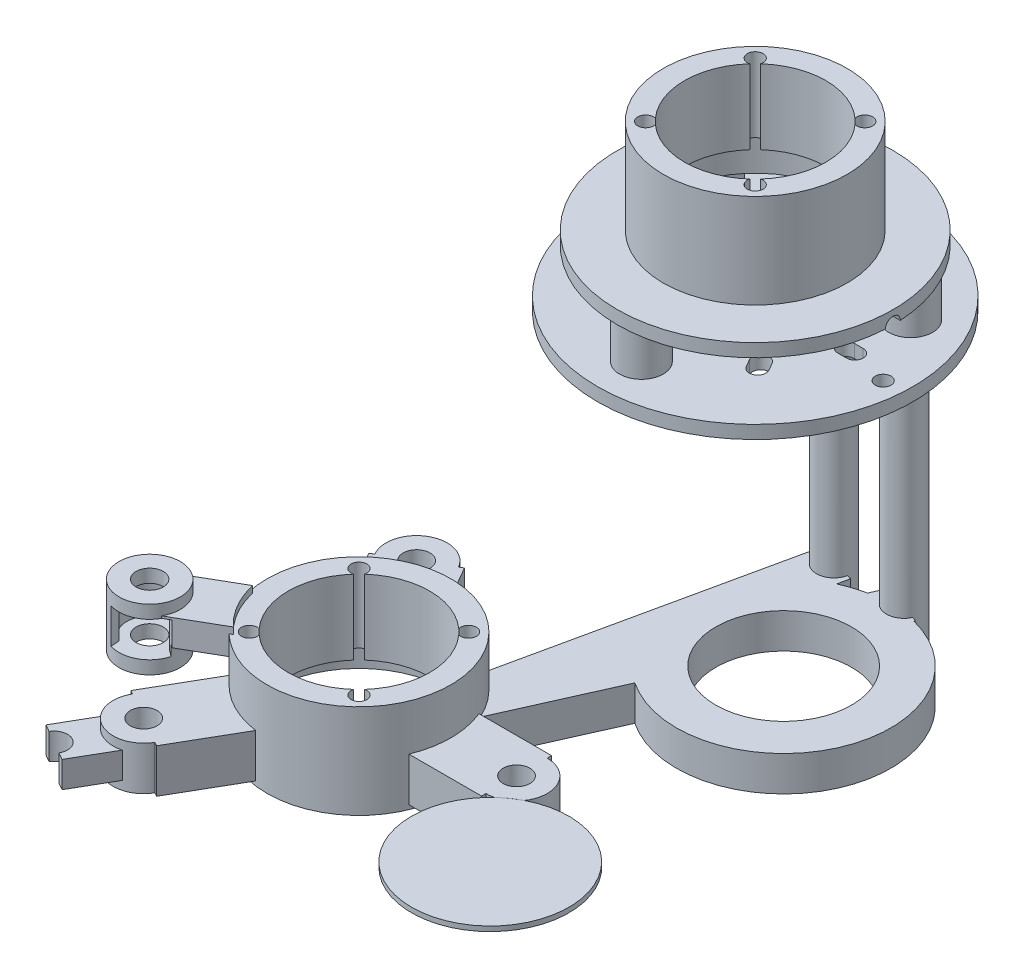
SolidWorks part; units mm, degrees
other "Driven Wheel Carrier and Motor Mount"
ref_plane "Front Plane" through (0, 0, 0) normal (0, 0, 1) x (1, 0, 0)
ref_plane "Top Plane" through (0, 0, 0) normal (0, 1, 0) x (1, 0, 0)
ref_plane "Right Plane" through (0, 0, 0) normal (1, 0, 0) x (0, 0, -1)
sketch3d "Carrier Inboard Frame Sketch datum points"
  point P0 (-56.2917, 132, 0)
  point P1 (-46.2917, 132, 0)
  point P2 (-56.2917, 132, -10)
ref_plane "Carrier Inboard Frame Sketch plane" through (0, 132, 0) normal (0, 1, 0) x (1, 0, 0)
sketch "Carrier Inboard Frame Sketch" plane through (0, 132, 0) normal (0, 1, 0) x (1, 0, 0)
  line L0 (-30.9178, 80.0952) -> (-31.8949, 80.3078)
  line L1 (-22.1235, 78.1819) -> (-23.1006, 78.3945)
  line L2 (-14.6632, 80.8722) -> (-15.5767, 81.279)
  line L3 (-6.4416, 77.2108) -> (-7.3551, 77.6176)
  line L4 (-31.8949, 80.3078) -> (-45.4534, 17.987)
  line L5 (-22.7017, 75.5241) -> (-22.1235, 78.1819)
  line L6 (-6.5333, 77.0049) -> (-6.4416, 77.2108)
  line L7 (-15.5767, 81.279) -> (-17.3672, 77.2584)
  line L8 (-67.3634, -35.1769) -> (-59.0717, -20.8152)
  line L9 (-72.9281, -12.8152) -> (-81.2199, -27.1769)
  line L10 (-81.2199, 27.1769) -> (-72.9281, 12.8152)
  line L11 (-59.0717, 20.8152) -> (-67.3634, 35.1769)
  line L12 (-37.065, 8.446) -> (-26.1713, 32.9078)
  line L13 (-20.2917, 8) -> (-36.8752, 8)
  line L14 (-36.8752, -8) -> (-20.2917, -8)
  line L15 (-20.2917, 7) -> (-20.2917, 8)
  line L16 (-20.2917, -8) -> (-20.2917, -7)
  line L17 (-80.3538, 27.6769) -> (-81.2199, 27.1769)
  line L18 (-67.3634, 35.1769) -> (-68.2295, 34.6769)
  line L19 (-68.2295, -34.6769) -> (-67.3634, -35.1769)
  line L20 (-81.2199, -27.1769) -> (-80.3538, -27.6769)
  line L21 (-14.5666, -4.0278) -> (-14.5523, -4.0074)
  line L22 (-81.0713, -32.9196) -> (-86.1218, -41.6673)
  line L23 (-77.4615, -46.6673) -> (-72.411, -37.9196)
  line L24 (-86.1218, -41.6673) -> (-84.4763, -42.6173)
  line L25 (-79.107, -45.7173) -> (-77.4615, -46.6673)
  arc A0 (-26.8341, 83.2411) -> (-30.9178, 80.0952) centre (-27.0092, 79.2449) ccw
  arc A1 (-23.1006, 78.3945) -> (-26.8341, 83.2411) centre (-27.0092, 79.2449) ccw
  arc A2 (-8.6179, 82.4514) -> (-14.6632, 80.8722) centre (-11.0092, 79.2449) ccw
  arc A3 (-7.3551, 77.6176) -> (-8.6179, 82.4514) centre (-11.0092, 79.2449) ccw
  arc A4 (-59.0717, 20.8152) -> (-45.4534, 17.987) centre (-56.2917, 0) cw
  arc A5 (-56.2917, -21) -> (-59.0717, -20.8152) centre (-56.2917, 0) cw
  arc A6 (-36.8752, -8) -> (-56.2917, -21) centre (-56.2917, 0) cw
  arc A7 (-72.9281, -12.8152) -> (-72.9281, 12.8152) centre (-56.2917, 0) cw
  arc A8 (-37.065, 8.446) -> (-36.8752, 8) centre (-56.2917, 0) cw
  arc A9 (-6.5333, 77.0049) -> (-26.1713, 32.9078) centre (-12.5092, 53.2449) cw
  arc A10 (-22.7017, 75.5241) -> (-17.3672, 77.2584) centre (-12.5092, 53.2449) cw
  circle A11 centre (-12.5092, 53.2449) radius 15.5
  arc A12 (-67.0768, -12.0209) -> (-68.3126, -10.7851) centre (-68.8074, -12.5158) cw
  arc A13 (-45.5065, -12.0209) -> (-67.0768, -12.0209) centre (-56.2917, 0) cw
  arc A14 (-68.3126, -10.7851) -> (-68.3126, 10.7851) centre (-56.2917, 0) cw
  arc A15 (-68.3126, 10.7851) -> (-67.0768, 12.0209) centre (-68.8074, 12.5158) cw
  arc A16 (-67.0768, 12.0209) -> (-45.5065, 12.0209) centre (-56.2917, 0) cw
  arc A17 (-45.5065, 12.0209) -> (-44.2707, 10.7851) centre (-43.7759, 12.5158) cw
  arc A18 (-44.2707, 10.7851) -> (-44.2707, -10.7851) centre (-56.2917, 0) cw
  arc A19 (-44.2707, -10.7851) -> (-45.5065, -12.0209) centre (-43.7759, -12.5158) cw
  arc A20 (-20.2917, -7) -> (-14.5666, -4.0278) centre (-20.2917, 0) ccw
  arc A21 (-14.5523, -4.0074) -> (-20.2917, 7) centre (-20.2917, 0) ccw
  circle A22 centre (-20.2917, 0) radius 3.05
  arc A23 (-68.2295, 34.6769) -> (-80.3538, 27.6769) centre (-74.2917, 31.1769) ccw
  circle A24 centre (-74.2917, 31.1769) radius 3.05
  arc A25 (-80.3538, -27.6769) -> (-81.0713, -32.9196) centre (-74.2917, -31.1769) ccw
  arc A26 (-72.411, -37.9196) -> (-68.2295, -34.6769) centre (-74.2917, -31.1769) ccw
  circle A27 centre (-74.2917, -31.1769) radius 3.05
  arc A28 (-84.4763, -42.6173) -> (-79.107, -45.7173) centre (-81.7917, -44.1673) cw
extrude "Carrier Inboard Frame" add sketch "Carrier Inboard Frame Sketch" against normal blind 4.5 separate body
sketch3d "Carrier Guide and Pivot Frame 2 Sketch datum points"
  point P0 (-56.2917, 132, 0)
  point P1 (-46.2917, 132, 0)
  point P2 (-56.2917, 132, -10)
ref_plane "Carrier Guide and Pivot Frame 2 Sketch plane" through (0, 132, 0) normal (0, 1, 0) x (1, 0, 0)
sketch "Carrier Guide and Pivot Frame 2 Sketch" plane through (0, 132, 0) normal (0, 1, 0) x (1, 0, 0)
  line L0 (-30.9178, 80.0952) -> (-31.8949, 80.3078)
  line L1 (-22.1235, 78.1819) -> (-23.1006, 78.3945)
  line L2 (-14.6632, 80.8722) -> (-15.5767, 81.279)
  line L3 (-6.4416, 77.2108) -> (-7.3551, 77.6176)
  line L4 (-31.8949, 80.3078) -> (-45.4534, 17.987)
  line L5 (-22.7017, 75.5241) -> (-22.1235, 78.1819)
  line L6 (-6.5333, 77.0049) -> (-6.4416, 77.2108)
  line L7 (-15.5767, 81.279) -> (-17.3672, 77.2584)
  line L8 (-67.3634, -35.1769) -> (-59.0717, -20.8152)
  line L9 (-72.9281, -12.8152) -> (-81.2199, -27.1769)
  line L10 (-81.2199, 27.1769) -> (-72.9281, 12.8152)
  line L11 (-59.0717, 20.8152) -> (-67.3634, 35.1769)
  line L12 (-37.065, 8.446) -> (-26.1713, 32.9078)
  line L13 (-20.2917, 8) -> (-36.8752, 8)
  line L14 (-36.8752, -8) -> (-20.2917, -8)
  line L15 (-20.2917, 7) -> (-20.2917, 8)
  line L16 (-20.2917, -8) -> (-20.2917, -7)
  line L17 (-80.3538, 27.6769) -> (-81.2199, 27.1769)
  line L18 (-67.3634, 35.1769) -> (-68.2295, 34.6769)
  line L19 (-68.2295, -34.6769) -> (-67.3634, -35.1769)
  line L20 (-81.2199, -27.1769) -> (-80.3538, -27.6769)
  line L21 (-14.5666, -4.0278) -> (-14.5523, -4.0074)
  arc A0 (-26.8341, 83.2411) -> (-30.9178, 80.0952) centre (-27.0092, 79.2449) ccw
  arc A1 (-23.1006, 78.3945) -> (-26.8341, 83.2411) centre (-27.0092, 79.2449) ccw
  arc A2 (-8.6179, 82.4514) -> (-14.6632, 80.8722) centre (-11.0092, 79.2449) ccw
  arc A3 (-7.3551, 77.6176) -> (-8.6179, 82.4514) centre (-11.0092, 79.2449) ccw
  arc A4 (-59.0717, 20.8152) -> (-45.4534, 17.987) centre (-56.2917, 0) cw
  arc A5 (-56.2917, -21) -> (-59.0717, -20.8152) centre (-56.2917, 0) cw
  arc A6 (-36.8752, -8) -> (-56.2917, -21) centre (-56.2917, 0) cw
  arc A7 (-72.9281, -12.8152) -> (-72.9281, 12.8152) centre (-56.2917, 0) cw
  arc A8 (-37.065, 8.446) -> (-36.8752, 8) centre (-56.2917, 0) cw
  arc A9 (-6.5333, 77.0049) -> (-26.1713, 32.9078) centre (-12.5092, 53.2449) cw
  arc A10 (-22.7017, 75.5241) -> (-17.3672, 77.2584) centre (-12.5092, 53.2449) cw
  circle A11 centre (-12.5092, 53.2449) radius 15.5
  arc A12 (-67.0768, -12.0209) -> (-68.3126, -10.7851) centre (-68.8074, -12.5158) cw
  arc A13 (-45.5065, -12.0209) -> (-67.0768, -12.0209) centre (-56.2917, 0) cw
  arc A14 (-68.3126, -10.7851) -> (-68.3126, 10.7851) centre (-56.2917, 0) cw
  arc A15 (-68.3126, 10.7851) -> (-67.0768, 12.0209) centre (-68.8074, 12.5158) cw
  arc A16 (-67.0768, 12.0209) -> (-45.5065, 12.0209) centre (-56.2917, 0) cw
  arc A17 (-45.5065, 12.0209) -> (-44.2707, 10.7851) centre (-43.7759, 12.5158) cw
  arc A18 (-44.2707, 10.7851) -> (-44.2707, -10.7851) centre (-56.2917, 0) cw
  arc A19 (-44.2707, -10.7851) -> (-45.5065, -12.0209) centre (-43.7759, -12.5158) cw
  arc A20 (-20.2917, -7) -> (-14.5666, -4.0278) centre (-20.2917, 0) ccw
  arc A21 (-14.5523, -4.0074) -> (-20.2917, 7) centre (-20.2917, 0) ccw
  circle A22 centre (-20.2917, 0) radius 3.05
  arc A23 (-68.2295, 34.6769) -> (-80.3538, 27.6769) centre (-74.2917, 31.1769) ccw
  circle A24 centre (-74.2917, 31.1769) radius 3.05
  arc A25 (-80.3538, -27.6769) -> (-72.411, -37.9196) centre (-74.2917, -31.1769) ccw
  arc A26 (-72.411, -37.9196) -> (-68.2295, -34.6769) centre (-74.2917, -31.1769) ccw
  circle A27 centre (-74.2917, -31.1769) radius 3.05
extrude "Carrier Guide and Pivot Frame 2" add sketch "Carrier Guide and Pivot Frame 2 Sketch" along normal blind 0.9
sketch3d "Carrier Guide and Pivot Frame 3 Sketch datum points"
  point P0 (-56.2917, 132.9, 0)
  point P1 (-46.2917, 132.9, 0)
  point P2 (-56.2917, 132.9, -10)
ref_plane "Carrier Guide and Pivot Frame 3 Sketch plane" through (0, 132.9, 0) normal (0, 1, 0) x (1, 0, 0)
sketch "Carrier Guide and Pivot Frame 3 Sketch" plane through (0, 132.9, 0) normal (0, 1, 0) x (1, 0, 0)
  line L0 (-30.9178, 80.0952) -> (-31.8949, 80.3078)
  line L1 (-22.1235, 78.1819) -> (-23.1006, 78.3945)
  line L2 (-14.6632, 80.8722) -> (-15.5767, 81.279)
  line L3 (-6.4416, 77.2108) -> (-7.3551, 77.6176)
  line L4 (-31.8949, 80.3078) -> (-45.4534, 17.987)
  line L5 (-22.7017, 75.5241) -> (-22.1235, 78.1819)
  line L6 (-6.5333, 77.0049) -> (-6.4416, 77.2108)
  line L7 (-15.5767, 81.279) -> (-17.3672, 77.2584)
  line L8 (-67.3634, -35.1769) -> (-59.0717, -20.8152)
  line L9 (-72.9281, -12.8152) -> (-81.2199, -27.1769)
  line L10 (-81.2199, 27.1769) -> (-72.9281, 12.8152)
  line L11 (-59.0717, 20.8152) -> (-67.3634, 35.1769)
  line L12 (-37.065, 8.446) -> (-26.1713, 32.9078)
  line L13 (-20.2917, 8) -> (-36.8752, 8)
  line L14 (-36.8752, -8) -> (-20.2917, -8)
  line L15 (-20.2917, 7) -> (-20.2917, 8)
  line L16 (-20.2917, -8) -> (-20.2917, -7)
  line L17 (-80.3538, 27.6769) -> (-81.2199, 27.1769)
  line L18 (-67.3634, 35.1769) -> (-68.2295, 34.6769)
  line L19 (-68.2295, -34.6769) -> (-67.3634, -35.1769)
  line L20 (-81.2199, -27.1769) -> (-80.3538, -27.6769)
  arc A0 (-26.8341, 83.2411) -> (-30.9178, 80.0952) centre (-27.0092, 79.2449) ccw
  arc A1 (-23.1006, 78.3945) -> (-26.8341, 83.2411) centre (-27.0092, 79.2449) ccw
  arc A2 (-8.6179, 82.4514) -> (-14.6632, 80.8722) centre (-11.0092, 79.2449) ccw
  arc A3 (-7.3551, 77.6176) -> (-8.6179, 82.4514) centre (-11.0092, 79.2449) ccw
  arc A4 (-59.0717, 20.8152) -> (-45.4534, 17.987) centre (-56.2917, 0) cw
  arc A5 (-56.2917, -21) -> (-59.0717, -20.8152) centre (-56.2917, 0) cw
  arc A6 (-36.8752, -8) -> (-56.2917, -21) centre (-56.2917, 0) cw
  arc A7 (-72.9281, -12.8152) -> (-72.9281, 12.8152) centre (-56.2917, 0) cw
  arc A8 (-37.065, 8.446) -> (-36.8752, 8) centre (-56.2917, 0) cw
  arc A9 (-6.5333, 77.0049) -> (-26.1713, 32.9078) centre (-12.5092, 53.2449) cw
  arc A10 (-22.7017, 75.5241) -> (-17.3672, 77.2584) centre (-12.5092, 53.2449) cw
  circle A11 centre (-12.5092, 53.2449) radius 15.5
  arc A12 (-67.0768, -12.0209) -> (-68.3126, -10.7851) centre (-68.8074, -12.5158) cw
  arc A13 (-45.5065, -12.0209) -> (-67.0768, -12.0209) centre (-56.2917, 0) cw
  arc A14 (-68.3126, -10.7851) -> (-68.3126, 10.7851) centre (-56.2917, 0) cw
  arc A15 (-68.3126, 10.7851) -> (-67.0768, 12.0209) centre (-68.8074, 12.5158) cw
  arc A16 (-67.0768, 12.0209) -> (-45.5065, 12.0209) centre (-56.2917, 0) cw
  arc A17 (-45.5065, 12.0209) -> (-44.2707, 10.7851) centre (-43.7759, 12.5158) cw
  arc A18 (-44.2707, 10.7851) -> (-44.2707, -10.7851) centre (-56.2917, 0) cw
  arc A19 (-44.2707, -10.7851) -> (-45.5065, -12.0209) centre (-43.7759, -12.5158) cw
  arc A20 (-20.2917, -7) -> (-18.4908, -6.7644) centre (-20.2917, 0) ccw
  arc A21 (-14.5523, -4.0074) -> (-20.2917, 7) centre (-20.2917, 0) ccw
  arc A22 (-18.4908, -6.7644) -> (-14.5523, -4.0074) centre (-6.2917, -20) ccw
  circle A23 centre (-20.2917, 0) radius 3.05
  arc A24 (-68.2295, 34.6769) -> (-80.3538, 27.6769) centre (-74.2917, 31.1769) ccw
  circle A25 centre (-74.2917, 31.1769) radius 3.05
  arc A26 (-80.3538, -27.6769) -> (-72.411, -37.9196) centre (-74.2917, -31.1769) ccw
  arc A27 (-72.411, -37.9196) -> (-68.2295, -34.6769) centre (-74.2917, -31.1769) ccw
  circle A28 centre (-74.2917, -31.1769) radius 3.05
extrude "Carrier Guide and Pivot Frame 3" add sketch "Carrier Guide and Pivot Frame 3 Sketch" along normal blind 0.1
sketch3d "Carrier Guide and Pivot Frame 4 Sketch datum points"
  point P0 (-56.2917, 133, 0)
  point P1 (-46.2917, 133, 0)
  point P2 (-56.2917, 133, -10)
ref_plane "Carrier Guide and Pivot Frame 4 Sketch plane" through (0, 133, 0) normal (0, 1, 0) x (1, 0, 0)
sketch "Carrier Guide and Pivot Frame 4 Sketch" plane through (0, 133, 0) normal (0, 1, 0) x (1, 0, 0)
  line L0 (-67.3634, -35.1769) -> (-59.0717, -20.8152)
  line L1 (-72.9281, -12.8152) -> (-81.2199, -27.1769)
  line L2 (-81.2199, 27.1769) -> (-72.9281, 12.8152)
  line L3 (-59.0717, 20.8152) -> (-67.3634, 35.1769)
  line L4 (-20.2917, 8) -> (-36.8752, 8)
  line L5 (-36.8752, -8) -> (-20.2917, -8)
  line L6 (-20.2917, 7) -> (-20.2917, 8)
  line L7 (-20.2917, -8) -> (-20.2917, -7)
  line L8 (-80.3538, 27.6769) -> (-81.2199, 27.1769)
  line L9 (-67.3634, 35.1769) -> (-68.2295, 34.6769)
  line L10 (-68.2295, -34.6769) -> (-67.3634, -35.1769)
  line L11 (-81.2199, -27.1769) -> (-80.3538, -27.6769)
  circle A0 centre (-27.0092, 79.2449) radius 4
  circle A1 centre (-11.0092, 79.2449) radius 4
  arc A2 (-56.2917, -21) -> (-59.0717, -20.8152) centre (-56.2917, 0) cw
  arc A3 (-36.8752, -8) -> (-56.2917, -21) centre (-56.2917, 0) cw
  arc A4 (-72.9281, -12.8152) -> (-72.9281, 12.8152) centre (-56.2917, 0) cw
  arc A5 (-59.0717, 20.8152) -> (-36.8752, 8) centre (-56.2917, 0) cw
  arc A6 (-67.0768, -12.0209) -> (-68.3126, -10.7851) centre (-68.8074, -12.5158) cw
  arc A7 (-45.5065, -12.0209) -> (-67.0768, -12.0209) centre (-56.2917, 0) cw
  arc A8 (-68.3126, -10.7851) -> (-68.3126, 10.7851) centre (-56.2917, 0) cw
  arc A9 (-68.3126, 10.7851) -> (-67.0768, 12.0209) centre (-68.8074, 12.5158) cw
  arc A10 (-67.0768, 12.0209) -> (-45.5065, 12.0209) centre (-56.2917, 0) cw
  arc A11 (-45.5065, 12.0209) -> (-44.2707, 10.7851) centre (-43.7759, 12.5158) cw
  arc A12 (-44.2707, 10.7851) -> (-44.2707, -10.7851) centre (-56.2917, 0) cw
  arc A13 (-44.2707, -10.7851) -> (-45.5065, -12.0209) centre (-43.7759, -12.5158) cw
  arc A14 (-20.2917, -7) -> (-18.4908, -6.7644) centre (-20.2917, 0) ccw
  arc A15 (-14.5523, -4.0074) -> (-20.2917, 7) centre (-20.2917, 0) ccw
  arc A16 (-18.4908, -6.7644) -> (-14.5523, -4.0074) centre (-6.2917, -20) ccw
  circle A17 centre (-20.2917, 0) radius 3.05
  arc A18 (-68.2295, 34.6769) -> (-80.3538, 27.6769) centre (-74.2917, 31.1769) ccw
  circle A19 centre (-74.2917, 31.1769) radius 3.05
  arc A20 (-80.3538, -27.6769) -> (-72.411, -37.9196) centre (-74.2917, -31.1769) ccw
  arc A21 (-72.411, -37.9196) -> (-68.2295, -34.6769) centre (-74.2917, -31.1769) ccw
  circle A22 centre (-74.2917, -31.1769) radius 3.05
extrude "Carrier Guide and Pivot Frame 4" add sketch "Carrier Guide and Pivot Frame 4 Sketch" along normal blind 1
sketch3d "Carrier Guide and Pivot Frame 5 Sketch datum points"
  point P0 (-56.2917, 134, 0)
  point P1 (-46.2917, 134, 0)
  point P2 (-56.2917, 134, -10)
ref_plane "Carrier Guide and Pivot Frame 5 Sketch plane" through (0, 134, 0) normal (0, 1, 0) x (1, 0, 0)
sketch "Carrier Guide and Pivot Frame 5 Sketch" plane through (0, 134, 0) normal (0, 1, 0) x (1, 0, 0)
  circle A0 centre (-27.0092, 79.2449) radius 4
  circle A1 centre (-11.0092, 79.2449) radius 4
  circle A2 centre (-56.2917, 0) radius 21
  arc A3 (-67.0768, -12.0209) -> (-68.3126, -10.7851) centre (-68.8074, -12.5158) cw
  arc A4 (-45.5065, -12.0209) -> (-67.0768, -12.0209) centre (-56.2917, 0) cw
  arc A5 (-68.3126, -10.7851) -> (-68.3126, 10.7851) centre (-56.2917, 0) cw
  arc A6 (-68.3126, 10.7851) -> (-67.0768, 12.0209) centre (-68.8074, 12.5158) cw
  arc A7 (-67.0768, 12.0209) -> (-45.5065, 12.0209) centre (-56.2917, 0) cw
  arc A8 (-45.5065, 12.0209) -> (-44.2707, 10.7851) centre (-43.7759, 12.5158) cw
  arc A9 (-44.2707, 10.7851) -> (-44.2707, -10.7851) centre (-56.2917, 0) cw
  arc A10 (-44.2707, -10.7851) -> (-45.5065, -12.0209) centre (-43.7759, -12.5158) cw
  circle A11 centre (-6.2917, -20) radius 18
extrude "Carrier Guide and Pivot Frame 5" add sketch "Carrier Guide and Pivot Frame 5 Sketch" along normal blind 0.01
sketch3d "Carrier Guide and Pivot Frame 6 Sketch datum points"
  point P0 (-56.2917, 134.01, 0)
  point P1 (-46.2917, 134.01, 0)
  point P2 (-56.2917, 134.01, -10)
ref_plane "Carrier Guide and Pivot Frame 6 Sketch plane" through (0, 134.01, 0) normal (0, 1, 0) x (1, 0, 0)
sketch "Carrier Guide and Pivot Frame 6 Sketch" plane through (0, 134.01, 0) normal (0, 1, 0) x (1, 0, 0)
  circle A0 centre (-27.0092, 79.2449) radius 4
  circle A1 centre (-11.0092, 79.2449) radius 4
  circle A2 centre (-56.2917, 0) radius 21
  arc A3 (-67.0768, -12.0209) -> (-68.3126, -10.7851) centre (-68.8074, -12.5158) cw
  arc A4 (-45.5065, -12.0209) -> (-67.0768, -12.0209) centre (-56.2917, 0) cw
  arc A5 (-68.3126, -10.7851) -> (-68.3126, 10.7851) centre (-56.2917, 0) cw
  arc A6 (-68.3126, 10.7851) -> (-67.0768, 12.0209) centre (-68.8074, 12.5158) cw
  arc A7 (-67.0768, 12.0209) -> (-45.5065, 12.0209) centre (-56.2917, 0) cw
  arc A8 (-45.5065, 12.0209) -> (-44.2707, 10.7851) centre (-43.7759, 12.5158) cw
  arc A9 (-44.2707, 10.7851) -> (-44.2707, -10.7851) centre (-56.2917, 0) cw
  arc A10 (-44.2707, -10.7851) -> (-45.5065, -12.0209) centre (-43.7759, -12.5158) cw
extrude "Carrier Guide and Pivot Frame 6" add sketch "Carrier Guide and Pivot Frame 6 Sketch" along normal blind 0.49
sketch3d "Carrier Guide and Pivot Frame 7 Sketch datum points"
  point P0 (-56.2917, 134.5, 0)
  point P1 (-46.2917, 134.5, 0)
  point P2 (-56.2917, 134.5, -10)
ref_plane "Carrier Guide and Pivot Frame 7 Sketch plane" through (0, 134.5, 0) normal (0, 1, 0) x (1, 0, 0)
sketch "Carrier Guide and Pivot Frame 7 Sketch" plane through (0, 134.5, 0) normal (0, 1, 0) x (1, 0, 0)
  circle A0 centre (-27.0092, 79.2449) radius 4
  circle A1 centre (-11.0092, 79.2449) radius 4
  circle A2 centre (-56.2917, 0) radius 21
  arc A3 (-67.0768, -12.0209) -> (-68.3126, -10.7851) centre (-68.8074, -12.5158) cw
  arc A4 (-45.5065, -12.0209) -> (-67.0768, -12.0209) centre (-56.2917, 0) cw
  arc A5 (-68.3126, -10.7851) -> (-68.3126, 10.7851) centre (-56.2917, 0) cw
  arc A6 (-68.3126, 10.7851) -> (-67.0768, 12.0209) centre (-68.8074, 12.5158) cw
  arc A7 (-67.0768, 12.0209) -> (-45.5065, 12.0209) centre (-56.2917, 0) cw
  arc A8 (-45.5065, 12.0209) -> (-44.2707, 10.7851) centre (-43.7759, 12.5158) cw
  arc A9 (-44.2707, 10.7851) -> (-44.2707, -10.7851) centre (-56.2917, 0) cw
  arc A10 (-44.2707, -10.7851) -> (-45.5065, -12.0209) centre (-43.7759, -12.5158) cw
  arc A11 (-80.48, -20.8934) -> (-80.8775, -21.5278) centre (-86.6025, -17.5) ccw
  arc A12 (-80.8775, -21.5278) -> (-80.48, -20.8934) centre (-86.6025, -17.5) ccw
  circle A13 centre (-86.6025, -17.5) radius 3.1
extrude "Carrier Guide and Pivot Frame 7" add sketch "Carrier Guide and Pivot Frame 7 Sketch" along normal blind 3
sketch3d "Carrier Guide and Pivot Frame 8 Sketch datum points"
  point P0 (-56.2917, 137.5, 0)
  point P1 (-46.2917, 137.5, 0)
  point P2 (-56.2917, 137.5, -10)
ref_plane "Carrier Guide and Pivot Frame 8 Sketch plane" through (0, 137.5, 0) normal (0, 1, 0) x (1, 0, 0)
sketch "Carrier Guide and Pivot Frame 8 Sketch" plane through (0, 137.5, 0) normal (0, 1, 0) x (1, 0, 0)
  line L0 (-81.3983, -18.1917) -> (-79.8556, -19.365)
  line L1 (-88.7258, -24.1702) -> (-88.866, -22.237)
  circle A0 centre (-27.0092, 79.2449) radius 4
  circle A1 centre (-11.0092, 79.2449) radius 4
  circle A2 centre (-56.2917, 0) radius 21
  arc A3 (-67.0768, -12.0209) -> (-68.3126, -10.7851) centre (-68.8074, -12.5158) cw
  arc A4 (-45.5065, -12.0209) -> (-67.0768, -12.0209) centre (-56.2917, 0) cw
  arc A5 (-68.3126, -10.7851) -> (-68.3126, 10.7851) centre (-56.2917, 0) cw
  arc A6 (-68.3126, 10.7851) -> (-67.0768, 12.0209) centre (-68.8074, 12.5158) cw
  arc A7 (-67.0768, 12.0209) -> (-45.5065, 12.0209) centre (-56.2917, 0) cw
  arc A8 (-45.5065, 12.0209) -> (-44.2707, 10.7851) centre (-43.7759, 12.5158) cw
  arc A9 (-44.2707, 10.7851) -> (-44.2707, -10.7851) centre (-56.2917, 0) cw
  arc A10 (-44.2707, -10.7851) -> (-45.5065, -12.0209) centre (-43.7759, -12.5158) cw
  arc A11 (-88.866, -22.237) -> (-81.3983, -18.1917) centre (-86.6025, -17.5) cw
  arc A12 (-79.8556, -19.365) -> (-88.7258, -24.1702) centre (-86.6025, -17.5) ccw
extrude "Carrier Guide and Pivot Frame 8" add sketch "Carrier Guide and Pivot Frame 8 Sketch" along normal blind 2.5
sketch3d "Carrier Guide and Pivot Frame 9 Sketch datum points"
  point P0 (-56.2917, 140, 0)
  point P1 (-46.2917, 140, 0)
  point P2 (-56.2917, 140, -10)
ref_plane "Carrier Guide and Pivot Frame 9 Sketch plane" through (0, 140, 0) normal (0, 1, 0) x (1, 0, 0)
sketch "Carrier Guide and Pivot Frame 9 Sketch" plane through (0, 140, 0) normal (0, 1, 0) x (1, 0, 0)
  line L0 (-78.9827, -20.0289) -> (-70.7201, -15.2585)
  line L1 (-76.7201, -4.8662) -> (-86.48, -10.5011)
  line L2 (-81.3983, -18.1917) -> (-78.9827, -20.0289)
  line L3 (-88.7258, -24.1702) -> (-88.866, -22.237)
  circle A0 centre (-27.0092, 79.2449) radius 4
  circle A1 centre (-11.0092, 79.2449) radius 4
  arc A2 (-56.2917, -21) -> (-70.7201, -15.2585) centre (-56.2917, 0) cw
  arc A3 (-76.7201, -4.8662) -> (-56.2917, -21) centre (-56.2917, 0) cw
  arc A4 (-86.48, -10.5011) -> (-88.7258, -24.1702) centre (-86.6025, -17.5) ccw
  arc A5 (-67.0768, -12.0209) -> (-68.3126, -10.7851) centre (-68.8074, -12.5158) cw
  arc A6 (-45.5065, -12.0209) -> (-67.0768, -12.0209) centre (-56.2917, 0) cw
  arc A7 (-68.3126, -10.7851) -> (-68.3126, 10.7851) centre (-56.2917, 0) cw
  arc A8 (-68.3126, 10.7851) -> (-67.0768, 12.0209) centre (-68.8074, 12.5158) cw
  arc A9 (-67.0768, 12.0209) -> (-45.5065, 12.0209) centre (-56.2917, 0) cw
  arc A10 (-45.5065, 12.0209) -> (-44.2707, 10.7851) centre (-43.7759, 12.5158) cw
  arc A11 (-44.2707, 10.7851) -> (-44.2707, -10.7851) centre (-56.2917, 0) cw
  arc A12 (-44.2707, -10.7851) -> (-45.5065, -12.0209) centre (-43.7759, -12.5158) cw
  arc A13 (-88.866, -22.237) -> (-81.3983, -18.1917) centre (-86.6025, -17.5) cw
extrude "Carrier Guide and Pivot Frame 9" add sketch "Carrier Guide and Pivot Frame 9 Sketch" along normal blind 4.5
sketch3d "Carrier Guide and Pivot Frame 10 Sketch datum points"
  point P0 (-56.2917, 144.5, 0)
  point P1 (-46.2917, 144.5, 0)
  point P2 (-56.2917, 144.5, -10)
ref_plane "Carrier Guide and Pivot Frame 10 Sketch plane" through (0, 144.5, 0) normal (0, 1, 0) x (1, 0, 0)
sketch "Carrier Guide and Pivot Frame 10 Sketch" plane through (0, 144.5, 0) normal (0, 1, 0) x (1, 0, 0)
  line L0 (-78.9827, -20.0289) -> (-70.0865, -14.8927)
  line L1 (-81.3983, -18.1917) -> (-78.9827, -20.0289)
  line L2 (-76.0865, -4.5004) -> (-86.48, -10.5011)
  line L3 (-88.7258, -24.1702) -> (-88.866, -22.237)
  circle A0 centre (-27.0092, 79.2449) radius 4
  circle A1 centre (-11.0092, 79.2449) radius 4
  arc A2 (-70.0865, -14.8927) -> (-76.0865, -4.5004) centre (-56.2917, 0) cw
  arc A3 (-86.48, -10.5011) -> (-88.7258, -24.1702) centre (-86.6025, -17.5) ccw
  arc A4 (-88.866, -22.237) -> (-81.3983, -18.1917) centre (-86.6025, -17.5) cw
extrude "Carrier Guide and Pivot Frame 10" add sketch "Carrier Guide and Pivot Frame 10 Sketch" along normal blind 1
sketch3d "Carrier Guide and Pivot Frame 11 Sketch datum points"
  point P0 (-56.2917, 145.5, 0)
  point P1 (-46.2917, 145.5, 0)
  point P2 (-56.2917, 145.5, -10)
ref_plane "Carrier Guide and Pivot Frame 11 Sketch plane" through (0, 145.5, 0) normal (0, 1, 0) x (1, 0, 0)
sketch "Carrier Guide and Pivot Frame 11 Sketch" plane through (0, 145.5, 0) normal (0, 1, 0) x (1, 0, 0)
  line L0 (-80.48, -20.8934) -> (-70.0865, -14.8927)
  line L1 (-76.0865, -4.5004) -> (-86.48, -10.5011)
  circle A0 centre (-27.0092, 79.2449) radius 4
  circle A1 centre (-11.0092, 79.2449) radius 4
  arc A2 (-80.8775, -21.5278) -> (-80.48, -20.8934) centre (-86.6025, -17.5) ccw
  arc A3 (-70.0865, -14.8927) -> (-76.0865, -4.5004) centre (-56.2917, 0) cw
  arc A4 (-86.48, -10.5011) -> (-80.8775, -21.5278) centre (-86.6025, -17.5) ccw
  circle A5 centre (-86.6025, -17.5) radius 3.1
extrude "Carrier Guide and Pivot Frame 11" add sketch "Carrier Guide and Pivot Frame 11 Sketch" along normal blind 0.5
sketch3d "Carrier Guide and Pivot Frame 12 Sketch datum points"
  point P0 (-56.2917, 146, 0)
  point P1 (-46.2917, 146, 0)
  point P2 (-56.2917, 146, -10)
ref_plane "Carrier Guide and Pivot Frame 12 Sketch plane" through (0, 146, 0) normal (0, 1, 0) x (1, 0, 0)
sketch "Carrier Guide and Pivot Frame 12 Sketch" plane through (0, 146, 0) normal (0, 1, 0) x (1, 0, 0)
  circle A0 centre (-27.0092, 79.2449) radius 4
  circle A1 centre (-11.0092, 79.2449) radius 4
  arc A2 (-80.8775, -21.5278) -> (-80.48, -20.8934) centre (-86.6025, -17.5) ccw
  arc A3 (-80.48, -20.8934) -> (-80.8775, -21.5278) centre (-86.6025, -17.5) ccw
  circle A4 centre (-86.6025, -17.5) radius 3.1
extrude "Carrier Guide and Pivot Frame 12" add sketch "Carrier Guide and Pivot Frame 12 Sketch" along normal blind 2.5
sketch3d "Carrier Wheel Support 13 Sketch datum points"
  point P0 (-56.2917, 148.5, 0)
  point P1 (-46.2917, 148.5, 0)
  point P2 (-56.2917, 148.5, -10)
ref_plane "Carrier Wheel Support 13 Sketch plane" through (0, 148.5, 0) normal (0, 1, 0) x (1, 0, 0)
sketch "Carrier Wheel Support 13 Sketch" plane through (0, 148.5, 0) normal (0, 1, 0) x (1, 0, 0)
  circle A0 centre (-27.0092, 79.2449) radius 4
  circle A1 centre (-11.0092, 79.2449) radius 4
extrude "Carrier Wheel Support 13" add sketch "Carrier Wheel Support 13 Sketch" along normal blind 43.5
sketch3d "Carrier Wheel Support 14 Sketch datum points"
  point P0 (-56.2917, 192, 0)
  point P1 (-46.2917, 192, 0)
  point P2 (-56.2917, 192, -10)
ref_plane "Carrier Wheel Support 14 Sketch plane" through (0, 192, 0) normal (0, 1, 0) x (1, 0, 0)
sketch "Carrier Wheel Support 14 Sketch" plane through (0, 192, 0) normal (0, 1, 0) x (1, 0, 0)
  arc A0 (-26.8341, 83.2411) -> (-24.8742, 75.8623) centre (-27.0092, 79.2449) ccw
  arc A1 (-23.3259, 77.685) -> (-26.8341, 83.2411) centre (-27.0092, 79.2449) ccw
  arc A2 (-24.8742, 75.8623) -> (-23.3259, 77.685) centre (-23.0746, 75.9026) cw
  circle A3 centre (-11.0092, 79.2449) radius 4
extrude "Carrier Wheel Support 14" add sketch "Carrier Wheel Support 14 Sketch" along normal blind 2.2
sketch3d "Carrier Wheel Support 15 Sketch datum points"
  point P0 (-56.2917, 194.2, 0)
  point P1 (-46.2917, 194.2, 0)
  point P2 (-56.2917, 194.2, -10)
ref_plane "Carrier Wheel Support 15 Sketch plane" through (0, 194.2, 0) normal (0, 1, 0) x (1, 0, 0)
sketch "Carrier Wheel Support 15 Sketch" plane through (0, 194.2, 0) normal (0, 1, 0) x (1, 0, 0)
  line L0 (-26.3746, 75.9026) -> (-26.0608, 75.3589)
  line L1 (-23.0386, 78.7605) -> (-24.7246, 78.7605)
  line L2 (-24.7246, 78.7605) -> (-26.3746, 75.9026)
  arc A0 (-26.8341, 83.2411) -> (-26.0608, 75.3589) centre (-27.0092, 79.2449) ccw
  arc A1 (-23.0386, 78.7605) -> (-26.8341, 83.2411) centre (-27.0092, 79.2449) ccw
  circle A2 centre (-11.0092, 79.2449) radius 4
extrude "Carrier Wheel Support 15" add sketch "Carrier Wheel Support 15 Sketch" along normal blind 2.9
sketch3d "Carrier Wheel Support 16 Sketch datum points"
  point P0 (-56.2917, 197.1, 0)
  point P1 (-46.2917, 197.1, 0)
  point P2 (-56.2917, 197.1, -10)
ref_plane "Carrier Wheel Support 16 Sketch plane" through (0, 197.1, 0) normal (0, 1, 0) x (1, 0, 0)
sketch "Carrier Wheel Support 16 Sketch" plane through (0, 197.1, 0) normal (0, 1, 0) x (1, 0, 0)
  arc A0 (-26.8341, 83.2411) -> (-24.8742, 75.8623) centre (-27.0092, 79.2449) ccw
  arc A1 (-23.3259, 77.685) -> (-26.8341, 83.2411) centre (-27.0092, 79.2449) ccw
  arc A2 (-24.8742, 75.8623) -> (-23.3259, 77.685) centre (-23.0746, 75.9026) cw
  circle A3 centre (-11.0092, 79.2449) radius 4
extrude "Carrier Wheel Support 16" add sketch "Carrier Wheel Support 16 Sketch" along normal blind 2.9
sketch3d "Carrier Wheel Support 17 Sketch datum points"
  point P0 (-56.2917, 200, 0)
  point P1 (-46.2917, 200, 0)
  point P2 (-56.2917, 200, -10)
ref_plane "Carrier Wheel Support 17 Sketch plane" through (0, 200, 0) normal (0, 1, 0) x (1, 0, 0)
sketch "Carrier Wheel Support 17 Sketch" plane through (0, 200, 0) normal (0, 1, 0) x (1, 0, 0)
  line L0 (-22.2871, 66.3808) -> (-21.2871, 64.6487)
  line L1 (-17.9962, 66.5487) -> (-18.9962, 68.2808)
  line L2 (-28.7742, 51.3449) -> (-26.7742, 51.3449)
  line L3 (-26.7742, 55.1449) -> (-28.7742, 55.1449)
  line L4 (-18.9962, 38.209) -> (-17.9962, 39.941)
  line L5 (-21.2871, 41.841) -> (-22.2871, 40.109)
  line L6 (-6.0221, 68.2808) -> (-7.0221, 66.5487)
  line L7 (-3.7312, 64.6487) -> (-2.7312, 66.3808)
  line L8 (3.7558, 55.1449) -> (1.7558, 55.1449)
  line L9 (1.7558, 51.3449) -> (3.7558, 51.3449)
  line L10 (-2.7312, 40.109) -> (-3.7312, 41.841)
  line L11 (-7.0221, 39.941) -> (-6.0221, 38.209)
  circle A0 centre (-19.0092, 53.2449) radius 36
  circle A1 centre (-23.0746, 75.9026) radius 1.8
  arc A2 (-22.2871, 66.3808) -> (-18.9962, 68.2808) centre (-20.6417, 67.3308) cw
  arc A3 (-17.9962, 66.5487) -> (-21.2871, 64.6487) centre (-19.6417, 65.5987) cw
  arc A4 (-28.7742, 51.3449) -> (-28.7742, 55.1449) centre (-28.7742, 53.2449) cw
  arc A5 (-26.7742, 55.1449) -> (-26.7742, 51.3449) centre (-26.7742, 53.2449) cw
  circle A6 centre (-26.8486, 32.7661) radius 1.8
  arc A7 (-18.9962, 38.209) -> (-22.2871, 40.109) centre (-20.6417, 39.159) cw
  arc A8 (-21.2871, 41.841) -> (-17.9962, 39.941) centre (-19.6417, 40.891) cw
  circle A9 centre (-19.0092, 53.2449) radius 5
  arc A10 (-6.0221, 68.2808) -> (-2.7312, 66.3808) centre (-4.3767, 67.3308) cw
  arc A11 (-3.7312, 64.6487) -> (-7.0221, 66.5487) centre (-5.3767, 65.5987) cw
  arc A12 (3.7558, 55.1449) -> (3.7558, 51.3449) centre (3.7558, 53.2449) cw
  arc A13 (1.7558, 51.3449) -> (1.7558, 55.1449) centre (1.7558, 53.2449) cw
  arc A14 (-2.7312, 40.109) -> (-6.0221, 38.209) centre (-4.3767, 39.159) cw
  arc A15 (-7.0221, 39.941) -> (-3.7312, 41.841) centre (-5.3767, 40.891) cw
  circle A16 centre (12.3957, 51.066) radius 1.8
extrude "Carrier Wheel Support 17" add sketch "Carrier Wheel Support 17 Sketch" along normal blind 3
sketch3d "Carrier Wheel Support 18 Sketch datum points"
  point P0 (-56.2917, 203, 0)
  point P1 (-46.2917, 203, 0)
  point P2 (-56.2917, 203, -10)
ref_plane "Carrier Wheel Support 18 Sketch plane" through (0, 203, 0) normal (0, 1, 0) x (1, 0, 0)
sketch "Carrier Wheel Support 18 Sketch" plane through (0, 203, 0) normal (0, 1, 0) x (1, 0, 0)
  circle A0 centre (-41.5258, 66.2449) radius 5
  arc A1 (-26.2217, 75.3232) -> (-23.0117, 79.102) centre (-23.0746, 75.9026) cw
  arc A2 (-26.8341, 83.2411) -> (-26.2217, 75.3232) centre (-27.0092, 79.2449) ccw
  arc A3 (-23.0117, 79.102) -> (-26.8341, 83.2411) centre (-27.0092, 79.2449) ccw
  circle A4 centre (-19.0092, 27.2449) radius 5
  circle A5 centre (-11.0092, 79.2449) radius 4
  arc A6 (3.5075, 61.2449) -> (-1.3886, 65.2306) centre (3.5075, 66.2449) cw
  arc A7 (-1.3287, 67.5144) -> (3.5075, 61.2449) centre (3.5075, 66.2449) cw
  arc A8 (-1.3287, 67.5144) -> (-1.3886, 65.2306) centre (-4.8767, 66.4648) cw
extrude "Carrier Wheel Support 18" add sketch "Carrier Wheel Support 18 Sketch" along normal blind 0.9
sketch3d "Carrier Wheel Support 19 Sketch datum points"
  point P0 (-56.2917, 203.9, 0)
  point P1 (-46.2917, 203.9, 0)
  point P2 (-56.2917, 203.9, -10)
ref_plane "Carrier Wheel Support 19 Sketch plane" through (0, 203.9, 0) normal (0, 1, 0) x (1, 0, 0)
sketch "Carrier Wheel Support 19 Sketch" plane through (0, 203.9, 0) normal (0, 1, 0) x (1, 0, 0)
  circle A0 centre (-41.5258, 66.2449) radius 5
  arc A1 (-26.2217, 75.3232) -> (-23.0117, 79.102) centre (-23.0746, 75.9026) cw
  arc A2 (-26.8341, 83.2411) -> (-26.2217, 75.3232) centre (-27.0092, 79.2449) ccw
  arc A3 (-23.0117, 79.102) -> (-26.8341, 83.2411) centre (-27.0092, 79.2449) ccw
  circle A4 centre (-19.0092, 27.2449) radius 5
  circle A5 centre (-11.0092, 79.2449) radius 4
  circle A6 centre (3.5075, 66.2449) radius 5
extrude "Carrier Wheel Support 19" add sketch "Carrier Wheel Support 19 Sketch" along normal blind 1.5
sketch3d "Carrier Wheel Support 20 Sketch datum points"
  point P0 (-56.2917, 205.4, 0)
  point P1 (-46.2917, 205.4, 0)
  point P2 (-56.2917, 205.4, -10)
ref_plane "Carrier Wheel Support 20 Sketch plane" through (0, 205.4, 0) normal (0, 1, 0) x (1, 0, 0)
sketch "Carrier Wheel Support 20 Sketch" plane through (0, 205.4, 0) normal (0, 1, 0) x (1, 0, 0)
  circle A0 centre (-41.5258, 66.2449) radius 5
  circle A1 centre (-27.0092, 79.2449) radius 4
  circle A2 centre (-19.0092, 27.2449) radius 5
  circle A3 centre (-11.0092, 79.2449) radius 4
  circle A4 centre (3.5075, 66.2449) radius 5
extrude "Carrier Wheel Support 20" add sketch "Carrier Wheel Support 20 Sketch" along normal blind 7.6
sketch3d "Carrier Wheel Support 21 Sketch datum points"
  point P0 (-56.2917, 213, 0)
  point P1 (-46.2917, 213, 0)
  point P2 (-56.2917, 213, -10)
ref_plane "Carrier Wheel Support 21 Sketch plane" through (0, 213, 0) normal (0, 1, 0) x (1, 0, 0)
sketch "Carrier Wheel Support 21 Sketch" plane through (0, 213, 0) normal (0, 1, 0) x (1, 0, 0)
  circle A0 centre (-19.0092, 53.2449) radius 31.5
  circle A1 centre (-19.0092, 53.2449) radius 20.15
extrude "Carrier Wheel Support 21" add sketch "Carrier Wheel Support 21 Sketch" along normal blind 3
sketch3d "Carrier Wheel Support 22 Sketch datum points"
  point P0 (-56.2917, 216, 0)
  point P1 (-46.2917, 216, 0)
  point P2 (-56.2917, 216, -10)
ref_plane "Carrier Wheel Support 22 Sketch plane" through (0, 216, 0) normal (0, 1, 0) x (1, 0, 0)
sketch "Carrier Wheel Support 22 Sketch" plane through (0, 216, 0) normal (0, 1, 0) x (1, 0, 0)
  circle A0 centre (-19.0092, 53.2449) radius 20.15
  circle A1 centre (-19.0092, 53.2449) radius 21
extrude "Carrier Wheel Support 22" add sketch "Carrier Wheel Support 22 Sketch" along normal blind 4.5
sketch3d "Carrier Wheel Support 23 Sketch datum points"
  point P0 (-56.2917, 220.5, 0)
  point P1 (-46.2917, 220.5, 0)
  point P2 (-56.2917, 220.5, -10)
ref_plane "Carrier Wheel Support 23 Sketch plane" through (0, 220.5, 0) normal (0, 1, 0) x (1, 0, 0)
sketch "Carrier Wheel Support 23 Sketch" plane through (0, 220.5, 0) normal (0, 1, 0) x (1, 0, 0)
  circle A0 centre (-19.0092, 53.2449) radius 21
  arc A1 (-31.0301, 42.4597) -> (-31.0301, 64.03) centre (-19.0092, 53.2449) cw
  arc A2 (-29.7943, 41.2239) -> (-31.0301, 42.4597) centre (-31.525, 40.7291) cw
  arc A3 (-31.0301, 64.03) -> (-29.7943, 65.2658) centre (-31.525, 65.7607) cw
  arc A4 (-8.224, 41.2239) -> (-29.7943, 41.2239) centre (-19.0092, 53.2449) cw
  arc A5 (-6.9882, 42.4597) -> (-8.224, 41.2239) centre (-6.4934, 40.7291) cw
  arc A6 (-6.9882, 64.03) -> (-6.9882, 42.4597) centre (-19.0092, 53.2449) cw
  arc A7 (-8.224, 65.2658) -> (-6.9882, 64.03) centre (-6.4934, 65.7607) cw
  arc A8 (-29.7943, 65.2658) -> (-8.224, 65.2658) centre (-19.0092, 53.2449) cw
extrude "Carrier Wheel Support 23" add sketch "Carrier Wheel Support 23 Sketch" along normal blind 17
sketch3d "Carrier Guide and Pivot Frame 24 Sketch datum points"
  point P0 (-56.2917, 127.5, 0)
  point P1 (-46.2917, 127.5, 0)
  point P2 (-56.2917, 127.5, -10)
ref_plane "Carrier Guide and Pivot Frame 24 Sketch plane" through (0, 127.5, 0) normal (0, 1, 0) x (1, 0, 0)
sketch "Carrier Guide and Pivot Frame 24 Sketch" plane through (0, 127.5, 0) normal (0, 1, 0) x (1, 0, 0)
  line L0 (-30.9178, 80.0952) -> (-31.8949, 80.3078)
  line L1 (-22.1235, 78.1819) -> (-23.1006, 78.3945)
  line L2 (-14.6632, 80.8722) -> (-15.5767, 81.279)
  line L3 (-6.4416, 77.2108) -> (-7.3551, 77.6176)
  line L4 (-31.8949, 80.3078) -> (-45.4534, 17.987)
  line L5 (-22.7017, 75.5241) -> (-22.1235, 78.1819)
  line L6 (-6.5333, 77.0049) -> (-6.4416, 77.2108)
  line L7 (-15.5767, 81.279) -> (-17.3672, 77.2584)
  line L8 (-67.3634, -35.1769) -> (-59.0717, -20.8152)
  line L9 (-72.9281, -12.8152) -> (-81.2199, -27.1769)
  line L10 (-81.2199, 27.1769) -> (-72.9281, 12.8152)
  line L11 (-59.0717, 20.8152) -> (-67.3634, 35.1769)
  line L12 (-37.065, 8.446) -> (-26.1713, 32.9078)
  line L13 (-20.2917, 8) -> (-36.8752, 8)
  line L14 (-36.8752, -8) -> (-20.2917, -8)
  line L15 (-20.2917, 7) -> (-20.2917, 8)
  line L16 (-20.2917, -8) -> (-20.2917, -7)
  line L17 (-80.3538, 27.6769) -> (-81.2199, 27.1769)
  line L18 (-67.3634, 35.1769) -> (-68.2295, 34.6769)
  line L19 (-68.2295, -34.6769) -> (-67.3634, -35.1769)
  line L20 (-81.2199, -27.1769) -> (-80.3538, -27.6769)
  line L21 (-14.5666, -4.0278) -> (-14.5523, -4.0074)
  line L22 (-81.0713, -32.9196) -> (-86.1218, -41.6673)
  line L23 (-77.4615, -46.6673) -> (-72.411, -37.9196)
  line L24 (-86.1218, -41.6673) -> (-84.4763, -42.6173)
  line L25 (-79.107, -45.7173) -> (-77.4615, -46.6673)
  arc A0 (-26.8341, 83.2411) -> (-30.9178, 80.0952) centre (-27.0092, 79.2449) ccw
  arc A1 (-23.1006, 78.3945) -> (-26.8341, 83.2411) centre (-27.0092, 79.2449) ccw
  arc A2 (-8.6179, 82.4514) -> (-14.6632, 80.8722) centre (-11.0092, 79.2449) ccw
  arc A3 (-7.3551, 77.6176) -> (-8.6179, 82.4514) centre (-11.0092, 79.2449) ccw
  arc A4 (-59.0717, 20.8152) -> (-45.4534, 17.987) centre (-56.2917, 0) cw
  arc A5 (-56.2917, -21) -> (-59.0717, -20.8152) centre (-56.2917, 0) cw
  arc A6 (-36.8752, -8) -> (-56.2917, -21) centre (-56.2917, 0) cw
  arc A7 (-72.9281, -12.8152) -> (-72.9281, 12.8152) centre (-56.2917, 0) cw
  arc A8 (-37.065, 8.446) -> (-36.8752, 8) centre (-56.2917, 0) cw
  arc A9 (-6.5333, 77.0049) -> (-26.1713, 32.9078) centre (-12.5092, 53.2449) cw
  arc A10 (-22.7017, 75.5241) -> (-17.3672, 77.2584) centre (-12.5092, 53.2449) cw
  circle A11 centre (-12.5092, 53.2449) radius 15.5
  circle A12 centre (-56.2917, 0) radius 20.15
  arc A13 (-20.2917, -7) -> (-14.5666, -4.0278) centre (-20.2917, 0) ccw
  arc A14 (-14.5523, -4.0074) -> (-20.2917, 7) centre (-20.2917, 0) ccw
  circle A15 centre (-20.2917, 0) radius 3.05
  arc A16 (-68.2295, 34.6769) -> (-80.3538, 27.6769) centre (-74.2917, 31.1769) ccw
  circle A17 centre (-74.2917, 31.1769) radius 3.05
  arc A18 (-80.3538, -27.6769) -> (-81.0713, -32.9196) centre (-74.2917, -31.1769) ccw
  arc A19 (-72.411, -37.9196) -> (-68.2295, -34.6769) centre (-74.2917, -31.1769) ccw
  circle A20 centre (-74.2917, -31.1769) radius 3.05
  arc A21 (-84.4763, -42.6173) -> (-79.107, -45.7173) centre (-81.7917, -44.1673) cw
extrude "Carrier Guide and Pivot Frame 24" add sketch "Carrier Guide and Pivot Frame 24 Sketch" against normal blind 1.5
sketch3d "Carrier Guide and Pivot Frame 25 Sketch datum points"
  point P0 (-56.2917, 126, 0)
  point P1 (-46.2917, 126, 0)
  point P2 (-56.2917, 126, -10)
ref_plane "Carrier Guide and Pivot Frame 25 Sketch plane" through (0, 126, 0) normal (0, 1, 0) x (1, 0, 0)
sketch "Carrier Guide and Pivot Frame 25 Sketch" plane through (0, 126, 0) normal (0, 1, 0) x (1, 0, 0)
  line L0 (-30.9178, 80.0952) -> (-31.8949, 80.3078)
  line L1 (-22.1235, 78.1819) -> (-23.1006, 78.3945)
  line L2 (-14.6632, 80.8722) -> (-15.5767, 81.279)
  line L3 (-6.4416, 77.2108) -> (-7.3551, 77.6176)
  line L4 (-31.8949, 80.3078) -> (-45.4534, 17.987)
  line L5 (-22.7017, 75.5241) -> (-22.1235, 78.1819)
  line L6 (-6.5333, 77.0049) -> (-6.4416, 77.2108)
  line L7 (-15.5767, 81.279) -> (-17.3672, 77.2584)
  line L8 (-67.3634, -35.1769) -> (-59.0717, -20.8152)
  line L9 (-72.9281, -12.8152) -> (-81.2199, -27.1769)
  line L10 (-81.2199, 27.1769) -> (-72.9281, 12.8152)
  line L11 (-59.0717, 20.8152) -> (-67.3634, 35.1769)
  line L12 (-37.065, 8.446) -> (-26.1713, 32.9078)
  line L13 (-20.2917, 8) -> (-36.8752, 8)
  line L14 (-36.8752, -8) -> (-20.2917, -8)
  line L15 (-20.2917, 7) -> (-20.2917, 8)
  line L16 (-20.2917, -8) -> (-20.2917, -7)
  line L17 (-80.3538, 27.6769) -> (-81.2199, 27.1769)
  line L18 (-67.3634, 35.1769) -> (-68.2295, 34.6769)
  line L19 (-68.2295, -34.6769) -> (-67.3634, -35.1769)
  line L20 (-81.2199, -27.1769) -> (-80.3538, -27.6769)
  line L21 (-14.5666, -4.0278) -> (-14.5523, -4.0074)
  arc A0 (-26.8341, 83.2411) -> (-30.9178, 80.0952) centre (-27.0092, 79.2449) ccw
  arc A1 (-23.1006, 78.3945) -> (-26.8341, 83.2411) centre (-27.0092, 79.2449) ccw
  arc A2 (-8.6179, 82.4514) -> (-14.6632, 80.8722) centre (-11.0092, 79.2449) ccw
  arc A3 (-7.3551, 77.6176) -> (-8.6179, 82.4514) centre (-11.0092, 79.2449) ccw
  arc A4 (-59.0717, 20.8152) -> (-45.4534, 17.987) centre (-56.2917, 0) cw
  arc A5 (-56.2917, -21) -> (-59.0717, -20.8152) centre (-56.2917, 0) cw
  arc A6 (-36.8752, -8) -> (-56.2917, -21) centre (-56.2917, 0) cw
  arc A7 (-72.9281, -12.8152) -> (-72.9281, 12.8152) centre (-56.2917, 0) cw
  arc A8 (-37.065, 8.446) -> (-36.8752, 8) centre (-56.2917, 0) cw
  arc A9 (-6.5333, 77.0049) -> (-26.1713, 32.9078) centre (-12.5092, 53.2449) cw
  arc A10 (-22.7017, 75.5241) -> (-17.3672, 77.2584) centre (-12.5092, 53.2449) cw
  circle A11 centre (-12.5092, 53.2449) radius 15.5
  circle A12 centre (-56.2917, 0) radius 20.15
  arc A13 (-20.2917, -7) -> (-14.5666, -4.0278) centre (-20.2917, 0) ccw
  arc A14 (-14.5523, -4.0074) -> (-20.2917, 7) centre (-20.2917, 0) ccw
  circle A15 centre (-20.2917, 0) radius 3.05
  arc A16 (-68.2295, 34.6769) -> (-80.3538, 27.6769) centre (-74.2917, 31.1769) ccw
  circle A17 centre (-74.2917, 31.1769) radius 3.05
  arc A18 (-80.3538, -27.6769) -> (-72.411, -37.9196) centre (-74.2917, -31.1769) ccw
  arc A19 (-72.411, -37.9196) -> (-68.2295, -34.6769) centre (-74.2917, -31.1769) ccw
  circle A20 centre (-74.2917, -31.1769) radius 3.05
extrude "Carrier Guide and Pivot Frame 25" add sketch "Carrier Guide and Pivot Frame 25 Sketch" against normal blind 1
sketch3d "Carrier Guide and Pivot Frame 26 Sketch datum points"
  point P0 (-56.2917, 125, 0)
  point P1 (-46.2917, 125, 0)
  point P2 (-56.2917, 125, -10)
ref_plane "Carrier Guide and Pivot Frame 26 Sketch plane" through (0, 125, 0) normal (0, 1, 0) x (1, 0, 0)
sketch "Carrier Guide and Pivot Frame 26 Sketch" plane through (0, 125, 0) normal (0, 1, 0) x (1, 0, 0)
  line L0 (-67.3634, -35.1769) -> (-59.0717, -20.8152)
  line L1 (-72.9281, -12.8152) -> (-81.2199, -27.1769)
  line L2 (-81.2199, 27.1769) -> (-72.9281, 12.8152)
  line L3 (-59.0717, 20.8152) -> (-67.3634, 35.1769)
  line L4 (-20.2917, 8) -> (-36.8752, 8)
  line L5 (-36.8752, -8) -> (-20.2917, -8)
  line L6 (-20.2917, 7) -> (-20.2917, 8)
  line L7 (-20.2917, -8) -> (-20.2917, -7)
  line L8 (-80.3538, 27.6769) -> (-81.2199, 27.1769)
  line L9 (-67.3634, 35.1769) -> (-68.2295, 34.6769)
  line L10 (-68.2295, -34.6769) -> (-67.3634, -35.1769)
  line L11 (-81.2199, -27.1769) -> (-80.3538, -27.6769)
  line L12 (-14.5666, -4.0278) -> (-14.5523, -4.0074)
  arc A0 (-56.2917, -21) -> (-59.0717, -20.8152) centre (-56.2917, 0) cw
  arc A1 (-36.8752, -8) -> (-56.2917, -21) centre (-56.2917, 0) cw
  arc A2 (-72.9281, -12.8152) -> (-72.9281, 12.8152) centre (-56.2917, 0) cw
  arc A3 (-59.0717, 20.8152) -> (-36.8752, 8) centre (-56.2917, 0) cw
  circle A4 centre (-56.2917, 0) radius 20.15
  arc A5 (-20.2917, -7) -> (-14.5666, -4.0278) centre (-20.2917, 0) ccw
  arc A6 (-14.5523, -4.0074) -> (-20.2917, 7) centre (-20.2917, 0) ccw
  circle A7 centre (-20.2917, 0) radius 3.05
  arc A8 (-68.2295, 34.6769) -> (-80.3538, 27.6769) centre (-74.2917, 31.1769) ccw
  circle A9 centre (-74.2917, 31.1769) radius 3.05
  arc A10 (-80.3538, -27.6769) -> (-72.411, -37.9196) centre (-74.2917, -31.1769) ccw
  arc A11 (-72.411, -37.9196) -> (-68.2295, -34.6769) centre (-74.2917, -31.1769) ccw
  circle A12 centre (-74.2917, -31.1769) radius 3.05
extrude "Carrier Guide and Pivot Frame 26" add sketch "Carrier Guide and Pivot Frame 26 Sketch" against normal blind 1
sketch3d "Carrier Guide and Pivot Frame 27 Sketch datum points"
  point P0 (-56.2917, 124, 0)
  point P1 (-46.2917, 124, 0)
  point P2 (-56.2917, 124, -10)
ref_plane "Carrier Guide and Pivot Frame 27 Sketch plane" through (0, 124, 0) normal (0, 1, 0) x (1, 0, 0)
sketch "Carrier Guide and Pivot Frame 27 Sketch" plane through (0, 124, 0) normal (0, 1, 0) x (1, 0, 0)
  circle A0 centre (-56.2917, 0) radius 21
  circle A1 centre (-56.2917, 0) radius 20.15
extrude "Carrier Guide and Pivot Frame 27" add sketch "Carrier Guide and Pivot Frame 27 Sketch" against normal blind 1
sketch3d "Coupling Pin Service Channel Sketch datum points"
  point P0 (-52.0092, 213, -53.2449)
  point P1 (-52.0092, 203, -53.2449)
  point P2 (-52.0092, 213, -43.2449)
ref_plane "Coupling Pin Service Channel Sketch plane" through (-52.0092, 0, 0) normal (-1, 0, 0) x (0, 0, 1)
sketch "Coupling Pin Service Channel Sketch" plane through (-52.0092, 0, 0) normal (-1, 0, 0) x (0, 0, 1)
  circle A0 centre (-53.2449, 213) radius 1.7
extrude "Coupling Pin Service Channel" cut sketch "Coupling Pin Service Channel Sketch" against normal blind 66
combine bodies "Join part sections" operation type add bodies to combine 130 110 108
